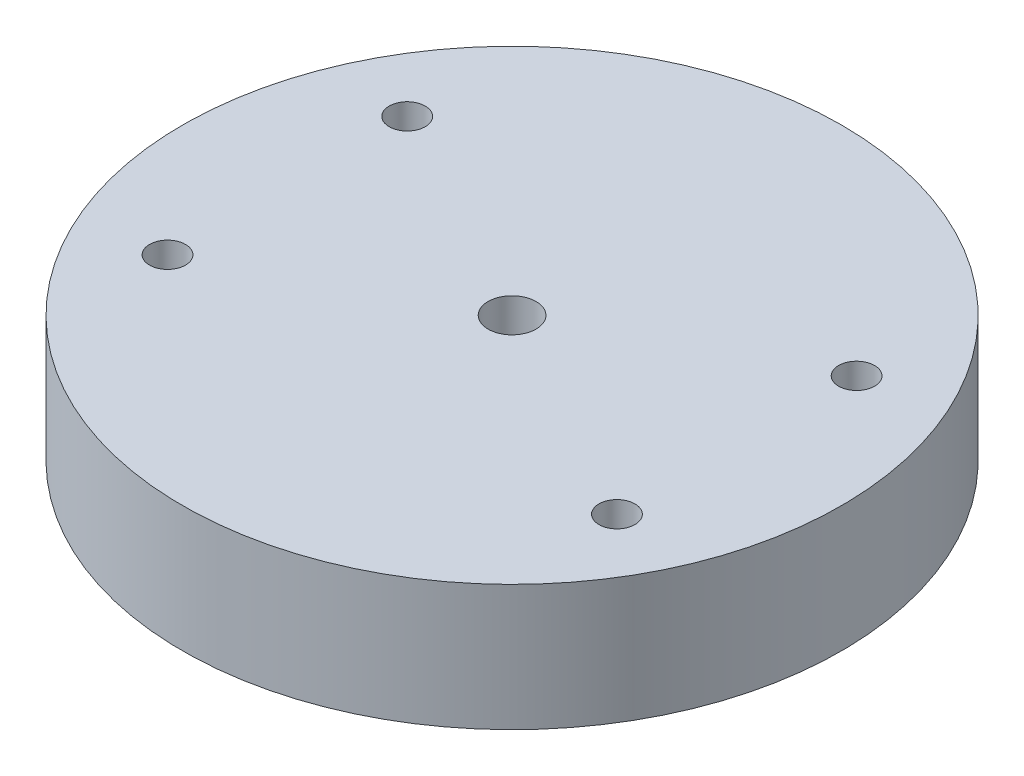
SolidWorks part; units mm, degrees
ref_plane "Front Plane" through (0, 0, 0) normal (0, 0, 1) x (1, 0, 0)
ref_plane "Top Plane" through (0, 0, 0) normal (0, 1, 0) x (1, 0, 0)
ref_plane "Right Plane" through (0, 0, 0) normal (1, 0, 0) x (0, 0, -1)
sketch "Sketch1" plane through (0, 0, 0) normal (0, 1, 0) x (1, 0, 0)
  circle A0 centre (0, 0) radius 55
  circle A1 centre (0, 0) radius 4
  dimension "D1" = 110
  dimension "D2" = 8
extrude "Boss-Extrude1" add sketch "Sketch1" along normal blind 21
sketch "Sketch2" plane through (0, 0, 0) normal (0, 1, 0) x (1, 0, 0)
  line L0 (-37.5, 0) -> (37.5, 0) construction
  line L1 (0, 0) -> (0, 55) construction
  line L2 (-37.5, -20) -> (-37.5, 20) construction
  line L3 (37.5, -20) -> (37.5, 20) construction
  circle A0 centre (0, 0) radius 55 construction
  circle A1 centre (-37.5, 20) radius 3
  circle A2 centre (-37.5, -20) radius 3
  circle A3 centre (37.5, -20) radius 3
  circle A4 centre (37.5, 20) radius 3
  dimension "D2" = 6
  dimension "D1" = 75
  dimension "D3" = 40
extrude "Cut-Extrude3" cut sketch "Sketch2" against normal blind 10 and the other way through all contours A4 | A3 | A2 | A1 region at (-37.5, 0, -20) region at (-37.5, 0, 20) region at (37.5, 0, 20) region at (37.5, 0, -20)
sketch "Sketch3" plane through (0, 0, 0) normal (0, 1, 0) x (1, 0, 0)
  line L0 (37.5, -20) -> (37.5, 20) construction
  line L1 (-37.5, -20) -> (-37.5, 20) construction
  line L2 (-37.5, 0) -> (37.5, 0) construction
  line L3 (37.5, -20) -> (37.5, 20) construction
  line L4 (-37.5, -20) -> (-37.5, 20) construction
  line L5 (-37.5, 0) -> (37.5, 0) construction
  line L6 (0, 0) -> (0, 55) construction
  line L7 (0, 0) -> (0, 55) construction
  circle A0 centre (-37.5, 20) radius 5
  circle A1 centre (-37.5, -20) radius 5
  circle A2 centre (37.5, 20) radius 5
  circle A3 centre (37.5, -20) radius 5
  dimension "D1" = 10
extrude "Cut-Extrude4" cut sketch "Sketch3" along normal blind 5
